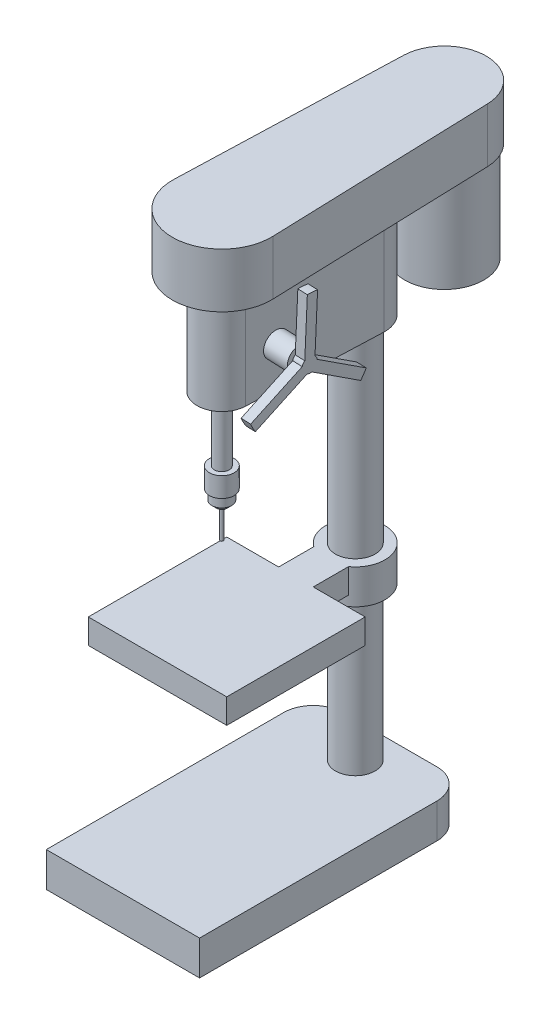
SolidWorks part; units mm, degrees
ref_plane "正面" through (0, 0, 0) normal (0, 0, 1) x (1, 0, 0)
ref_plane "平面" through (0, 0, 0) normal (0, 1, 0) x (1, 0, 0)
ref_plane "右側面" through (0, 0, 0) normal (1, 0, 0) x (0, 0, -1)
sketch "ｽｹｯﾁ1" plane through (0, 0, 0) normal (0, 1, 0) x (1, 0, 0)
  line L1 (0, 0) -> (310, 0)
  line L2 (0, 0) -> (0, 540)
  line L3 (0, 540) -> (310, 540)
  line L4 (310, 0) -> (310, 540)
  dimension "D1" = 310
  dimension "D2" = 540
extrude "ﾎﾞｽ - 押し出し1" add sketch "ｽｹｯﾁ1" along normal blind 70
fillet "ﾌｨﾚｯﾄ1" radius 60 2 edges at (0, 35, -540) (310, 35, -540)
sketch "ｽｹｯﾁ2" plane through (0, 70, 0) normal (0, 1, 0) x (1, 0, 0)
  line L0 (310, 0) -> (310, 480) construction
  line L1 (250, 540) -> (60, 540) construction
  circle A0 centre (155, 470) radius 40
  dimension "D1" = 80
  dimension "D2" = 155
  dimension "D3" = 70
extrude "ﾎﾞｽ - 押し出し2" add sketch "ｽｹｯﾁ2" along normal blind 310
sketch "ｽｹｯﾁ3" plane through (0, 380, 0) normal (0, 1, 0) x (1, 0, 0)
  circle A0 centre (155, 470) radius 60
  dimension "D1" = 120
extrude "ﾎﾞｽ - 押し出し3" add sketch "ｽｹｯﾁ3" along normal blind 20
sketch "ｽｹｯﾁ4" plane through (0, 400, 0) normal (0, 1, 0) x (1, 0, 0)
  line L0 (190, 350) -> (295, 350)
  line L1 (15, 70) -> (295, 70)
  line L2 (15, 70) -> (15, 350)
  line L3 (15, 350) -> (120, 350)
  line L4 (295, 70) -> (295, 350)
  line L6 (120, 421.266) -> (120, 350)
  line L8 (190, 421.266) -> (190, 350)
  arc A0 (190, 421.266) -> (120, 421.266) centre (155, 470) ccw
  dimension "D1" = 120
  dimension "D2" = 280
  dimension "D3" = 280
  dimension "D4" = 140
  dimension "D5" = 35
  dimension "D6" = 120
  dimension "D8" = 35
extrude "ﾎﾞｽ - 押し出し4" add sketch "ｽｹｯﾁ4" along normal blind 50
sketch "ｽｹｯﾁ5" plane through (0, 450, 0) normal (0, 1, 0) x (1, 0, 0)
  circle A0 centre (155, 470) radius 40
  dimension "D1" = 80
extrude "ﾎﾞｽ - 押し出し5" add sketch "ｽｹｯﾁ5" along normal blind 400
sketch "ｽｹｯﾁ8" plane through (0, 850, 0) normal (0, 1, 0) x (1, 0, 0)
  line L0 (95.0412, 467.7778) -> (105.0343, 198.1481)
  line L1 (214.9588, 467.7778) -> (204.9657, 198.1481)
  arc A0 (214.9588, 467.7778) -> (95.0412, 467.7778) centre (155, 470) ccw
  circle A1 centre (155, 470) radius 40 construction
  arc A2 (105.0343, 198.1481) -> (204.9657, 198.1481) centre (155, 200) ccw
  dimension "D1" = 120
  dimension "100" = 100
  dimension "D3" = 270
extrude "ﾎﾞｽ - 押し出し6" add sketch "ｽｹｯﾁ8" along normal blind 210
sketch "ｽｹｯﾁ9" plane through (0, 1060, 0) normal (0, 1, 0) x (1, 0, 0)
  line L0 (55.0556, 203.3333) -> (70.0472, 652.8333)
  line L1 (239.9528, 652.8333) -> (254.9444, 203.3333)
  arc A0 (239.9528, 652.8333) -> (70.0472, 652.8333) centre (155, 650) ccw
  arc A1 (55.0556, 203.3333) -> (254.9444, 203.3333) centre (155, 200) ccw
  arc A3 (105.0343, 198.1481) -> (204.9657, 198.1481) centre (155, 200) ccw construction
  dimension "D1" = 170
  dimension "D2" = 200
  dimension "D3" = 450
extrude "ﾎﾞｽ - 押し出し7" add sketch "ｽｹｯﾁ9" along normal blind 110
sketch "ｽｹｯﾁ10" plane through (0, 1060, 0) normal (0, -1, 0) x (-1, 0, 0)
  circle A0 centre (-155, 650) radius 80
  arc A1 (-70.0472, 652.8333) -> (-239.9528, 652.8333) centre (-155, 650) ccw construction
  dimension "D1" = 160
extrude "ﾎﾞｽ - 押し出し8" add sketch "ｽｹｯﾁ10" along normal blind 200
sketch "ｽｹｯﾁ11" plane through (0, 850, 0) normal (0, -1, 0) x (-1, 0, 0)
  circle A0 centre (-155, 200) radius 15
  arc A1 (-204.9657, 198.1481) -> (-105.0343, 198.1481) centre (-155, 200) ccw construction
  dimension "D1" = 30
extrude "ﾎﾞｽ - 押し出し9" add sketch "ｽｹｯﾁ11" along normal blind 130
sketch "ｽｹｯﾁ12" plane through (0, 720, 0) normal (0, -1, 0) x (-1, 0, 0)
  circle A0 centre (-155, 200) radius 25
  circle A1 centre (-155, 200) radius 15 construction
  dimension "D1" = 50
extrude "ﾎﾞｽ - 押し出し10" add sketch "ｽｹｯﾁ12" along normal blind 40
sketch "ｽｹｯﾁ13" plane through (0, 680, 0) normal (0, -1, 0) x (-1, 0, 0)
  circle A0 centre (-155, 200) radius 20
  circle A1 centre (-155, 200) radius 25 construction
  dimension "D1" = 40
extrude "ﾎﾞｽ - 押し出し11" add sketch "ｽｹｯﾁ13" along normal blind 30
chamfer "面取り1" distance 10 angle 45 1 edges at (155, 650, -220)
sketch "ｽｹｯﾁ14" plane through (0, 650, 0) normal (0, -1, 0) x (-1, 0, 0)
  circle A0 centre (-155, 200) radius 3.5
  circle A1 centre (-155, 200) radius 10 construction
  dimension "D1" = 7
extrude "ﾎﾞｽ - 押し出し12" add sketch "ｽｹｯﾁ14" along normal blind 60
sketch "ｽｹｯﾁ15" plane through (197.3507, 0, 7.3143) normal (0.9993, 0, 0.037) x (0.037, 0, -0.9993)
  line L0 (205.6035, 850) -> (475.4183, 850) construction
  line L1 (205.6035, 1060) -> (205.6035, 850) construction
  circle A0 centre (265.6035, 930) radius 25
  dimension "D1" = 50
  dimension "D2" = 80
  dimension "D3" = 60
extrude "ﾎﾞｽ - 押し出し13" add sketch "ｽｹｯﾁ15" along normal blind 50
sketch "ｽｹｯﾁ16" plane through (247.3164, 0, 9.1662) normal (0.9993, 0, 0.037) x (0.037, 0, -0.9993)
  circle A0 centre (265.6035, 930) radius 125
  circle A1 centre (265.6035, 930) radius 25 construction
  dimension "D1" = 250
extrude "ﾎﾞｽ - 押し出し14" add sketch "ｽｹｯﾁ16" along normal blind 20
sketch "ｽｹｯﾁ17" plane through (267.3027, 0, 9.9069) normal (0.9993, 0, 0.037) x (0.037, 0, -0.9993)
  line L0 (265.6035, 930) -> (313.5013, 899.4343) construction
  line L1 (265.6035, 930) -> (207.6336, 899.879) construction
  line L2 (265.6035, 930) -> (268.4104, 993.1809) construction
  line L3 (251.0718, 933.7187) -> (150.4279, 881.4244)
  line L5 (159.6494, 863.6772) -> (260.2932, 915.9714)
  line L6 (269.6489, 915.5558) -> (365.259, 854.5428)
  line L7 (280.4078, 932.4154) -> (376.0179, 871.4024)
  line L8 (276.0899, 940.7255) -> (281.1236, 1054.0328)
  line L9 (256.1096, 941.6131) -> (261.1433, 1054.9204)
  circle A0 centre (265.6035, 930) radius 125 construction
  arc A1 (260.2932, 915.9714) -> (269.6489, 915.5558) centre (265.6035, 930) ccw
  circle A2 centre (265.6035, 930) radius 125
  arc A3 (256.1096, 941.6131) -> (251.0718, 933.7187) centre (265.6035, 930) ccw
  arc A4 (280.4078, 932.4154) -> (276.0899, 940.7255) centre (265.6035, 930) ccw
  circle M1 centre (265.6035, 930) radius 125
  dimension "D3" = 30
  dimension "D10" = 250
  dimension "D1" = 120
  dimension "D2" = 120
  dimension "D4" = 20
  dimension "D5" = 20
  dimension "D6" = 10
  dimension "D7" = 10
  dimension "D8" = 20
  dimension "D9" = 10
extrude "ｶｯﾄ - 押し出し1" cut sketch "ｽｹｯﾁ17" against normal blind 20 contours A3 L9 L3 M1 | A4 L7 L8 M1 | A1 L5 L6 M1 region at (274.807, 970.1952, -192.5699) region at (277.0171, 855.3534, -252.2004) region at (279.5956, 964.4514, -321.7729)
scale "ｽｹｰﾙ1" scale about centroid uniform scaling yes scale factor 0.8
